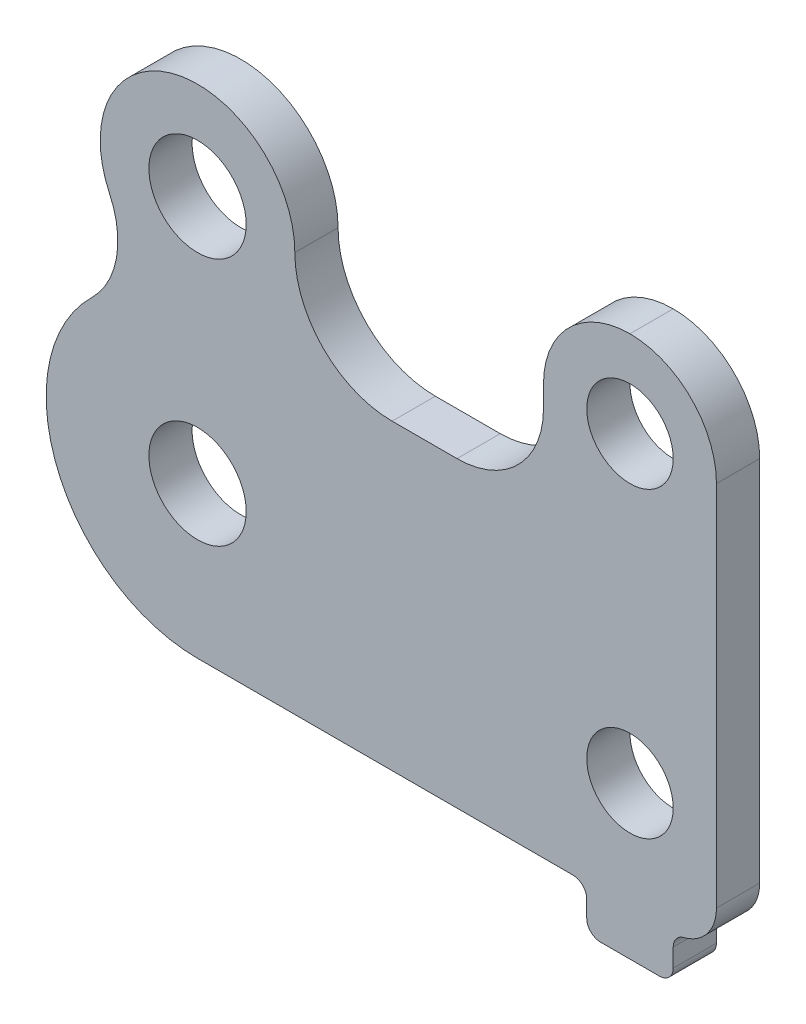
SolidWorks part; units mm, degrees
ref_plane "Front Plane" through (0, 0, 0) normal (0, 0, 1) x (1, 0, 0)
ref_plane "Top Plane" through (0, 0, 0) normal (0, 1, 0) x (1, 0, 0)
ref_plane "Right Plane" through (0, 0, 0) normal (1, 0, 0) x (0, 0, -1)
sketch "Sketch2" plane through (0, 0, 0) normal (0, 0, 1) x (1, 0, 0)
  line L0 (0, 5.5562) -> (12.7, 5.5562)
  line L1 (12.7, 5.5562) -> (12.7, -5.5562) construction
  line L2 (12.7, -5.5562) -> (0, -5.5562)
  line L3 (12.7, 5.5562) -> (12.7, 13.4938)
  line L4 (12.7, 13.4938) -> (19.05, 13.4937)
  line L5 (19.05, 13.4937) -> (19.05, -5.5562)
  line L6 (19.05, -5.5562) -> (12.7, -5.5562)
  line L7 (15.875, 9.525) -> (15.875, -1.5875) construction
  line L8 (14.2875, -5.5562) -> (14.2875, -7.1818)
  line L9 (14.2875, -7.1818) -> (17.4625, -7.1818)
  line L10 (17.4625, -7.1818) -> (17.4625, -5.5562)
  line L11 (0, 0) -> (0, -9.1281) construction
  line L12 (7.1437, 12.7) -> (12.7, 12.7)
  line L14 (12.7, 12.7) -> (19.05, 12.7)
  line L15 (0, 12.7) -> (7.1437, 12.7)
  circle A0 centre (0, 0) radius 1.7859
  circle A1 centre (0, 0) radius 5.5562
  circle A2 centre (0, 9.1281) radius 1.7859
  circle A3 centre (0, 9.1281) radius 3.5719
  circle A4 centre (0, 0) radius 9.1281 construction
  circle A5 centre (15.875, 9.525) radius 1.5875
  circle A6 centre (15.875, -1.5875) radius 1.5875
  circle A7 centre (-6.1005, 6.2465) radius 3.175
  circle A8 centre (7.1437, 9.1281) radius 3.5719
  circle A9 centre (0, 0) radius 12.7 construction
  circle A11 centre (7.1437, 9.1281) radius 1.7859 construction
  point P17 (15.875, 3.9688)
  point P18 (19.05, 3.9688)
  point P21 (15.875, -5.5562)
  point P25 (15.875, -7.1818)
  dimension "D1" = 3.5719
  dimension "D2" = 11.1125
  dimension "D5" = 7.1437
  dimension "D7" = 3.175
  dimension "D6" = 6.35
  dimension "D3" = 11.1125
  dimension "D4" = 6.35
  dimension "D8" = 3.175
  dimension "D9" = 1.6256
  dimension "D10" = 19.05
extrude "Boss-Extrude1" add sketch "Sketch2" along normal blind 1.5875 contours A1 L2 L6 L5 L4 L3 L0 A6 A5 | L9 L10 L6 L8 | A8 A3 L0 | A1 A0 | A7 A1 A3 | A3 A2 region at (3.5719, 6.3541, 0) region at (12.3012, 1.8224, 0) region at (3.8177, 3.8177, 0) region at (-1.8576, 6.1962, 0) region at (-2.3434, 5.6656, 0) region at (15.875, -6.369, 0)
fillet "Fillet1" radius 3.175 3 edges at (12.7, 5.5562, 0.7937) (12.7, 12.7, 0.7937) (19.05, 12.7, 0.7937)
fillet "Fillet3" radius 1.5875 1 edges at (19.05, -5.5562, 0.7937)
fillet "Fillet2" radius 0.508 4 edges at (14.2875, -7.1818, 0.7937) (17.4625, -7.1818, 0.7937) (14.2875, -5.5562, 0.7937) (17.4625, -5.5562, 0.7937)
